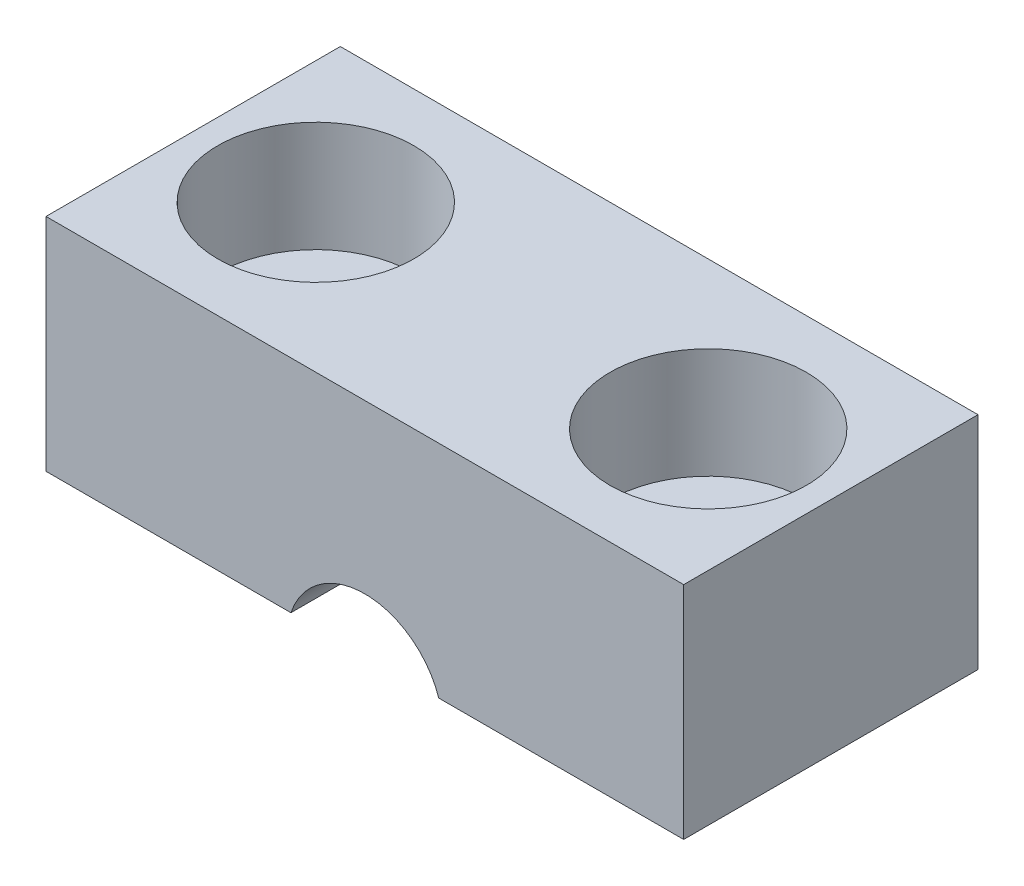
SolidWorks part; units mm, degrees
ref_plane "Front Plane" through (0, 0, 0) normal (0, 0, 1) x (1, 0, 0)
ref_plane "Top Plane" through (0, 0, 0) normal (0, 1, 0) x (1, 0, 0)
ref_plane "Right Plane" through (0, 0, 0) normal (1, 0, 0) x (0, 0, -1)
ref_plane "Plane1" through (0, 35, 0) normal (0, 1, 0) x (1, 0, 0)
sketch "Sketch1" plane through (0, 35, 0) normal (0, 1, 0) x (1, 0, 0)
  line L0 (13, 6) -> (-13, 6)
  line L1 (-13, 6) -> (-13, -6)
  line L2 (-13, -6) -> (13, -6)
  line L3 (13, -6) -> (13, 6)
extrude "Boss-Extrude1" add sketch "Sketch1" against normal blind 9
sketch "Sketch2" plane through (0, 0, -6) normal (0, 0, -1) x (-1, 0, 0)
  line L0 (-3.0134, 26) -> (3.0134, 26)
  line L2 (-13, 26) -> (13, 26) construction
  arc A0 (3.0134, 26) -> (-3.0134, 26) centre (0, 25) ccw
  point P10 (0, 26)
  dimension "D1" = 3.175
  dimension "D2" = 1
extrude "Cut-Extrude1" cut sketch "Sketch2" against normal through all
hole_wizard "CBORE for M4 Hex Head Machine Screw1" positions "Sketch4" profile "Sketch3" counterbore size "M4" standard "ANSI Metric"
sketch "Sketch4" plane through (0, 35, 0) normal (0, 1, 0) x (1, 0, 0)
  point P0 (-8, 0)
  point P1 (8, 0)
sketch "Sketch3" plane through (-8, 35, 0) normal (1, 0, 0) x (0, 0, 1)
  line L0 (0, 0) -> (0, 9)
  line L1 (0, 9) -> (2.25, 9)
  line L3 (2.25, 9) -> (2.25, 4.5)
  line L4 (2.25, 4.5) -> (4, 4.5)
  line L5 (4, 4.5) -> (4, 0)
  line L7 (4, 0) -> (0, 0)
  line L11 (0, -6.35) -> (0, 107.95) construction
  dimension "Thru Hole Dia." = 4.5
  dimension "Thru Hole Depth" = 9
  dimension "C'Bore Dia." = 8
  dimension "C'Bore Depth" = 4.5
